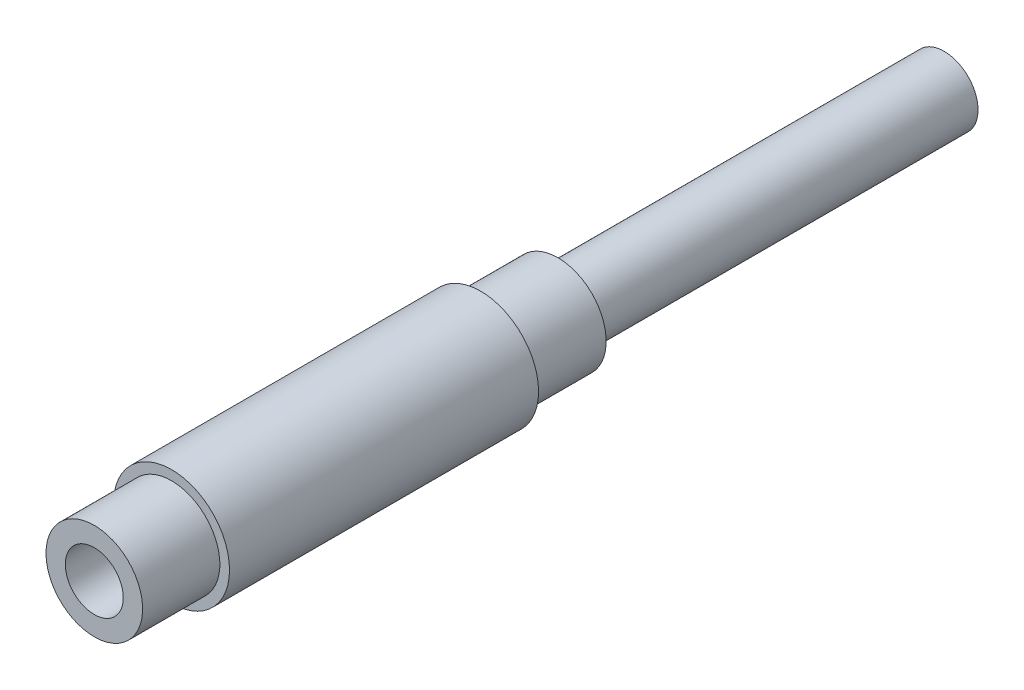
SolidWorks part; units mm, degrees
ref_plane "Front Plane" through (0, 0, 0) normal (0, 0, 1) x (1, 0, 0)
ref_plane "Top Plane" through (0, 0, 0) normal (0, 1, 0) x (1, 0, 0)
ref_plane "Right Plane" through (0, 0, 0) normal (1, 0, 0) x (0, 0, -1)
sketch "Sketch1" plane through (0, 0, 0) normal (0, 0, 1) x (1, 0, 0)
  circle A0 centre (0, 0) radius 7.9375
  dimension "D1" = 15.875
extrude "Boss-Extrude1" add sketch "Sketch1" along normal blind 76.2
sketch "Sketch4" plane through (0, 0, 0) normal (0, 0, -1) x (-1, 0, 0)
  circle A0 centre (0, 0) radius 5.5626
  dimension "D1" = 11.1252
extrude "Boss-Extrude2" add sketch "Sketch4" along normal blind 63.5
ref_plane "Plane1" through (0, 0, 12.7) normal (0, 0, 1) x (1, 0, 0)
sketch "Sketch6" plane through (0, 0, 12.7) normal (0, 0, 1) x (1, 0, 0)
  circle A0 centre (0, 0) radius 9.525
  circle A1 centre (0, 0) radius 7.9375
  circle A3 centre (0, 0) radius 7.9375 construction
  dimension "D1" = 19.05
extrude "Boss-Extrude4" add sketch "Sketch6" along normal offset from surface (50.8 mm away) 12.7 contours A0 up to face at (7.9375, 0, 76.2)
sketch "Sketch3" plane through (0, 0, 76.2) normal (0, 0, 1) x (1, 0, 0)
  circle A0 centre (0, 0) radius 4.7625
  dimension "D1" = 9.525
extrude "Cut-Extrude2" cut sketch "Sketch3" against normal blind 63.5
